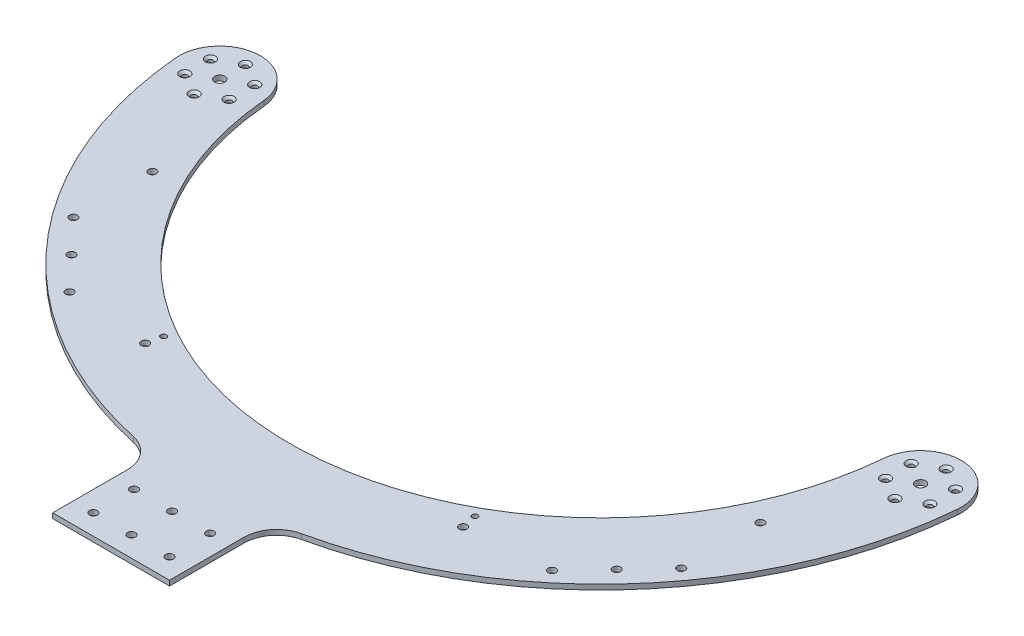
SolidWorks part; units mm, degrees
material "6061-T6 (SS)"
ref_plane "Front" through (0, 0, 0) normal (0, 0, 1) x (1, 0, 0)
ref_plane "Top" through (0, 0, 0) normal (0, 1, 0) x (1, 0, 0)
ref_plane "Right" through (0, 0, 0) normal (1, 0, 0) x (0, 0, -1)
sketch "Sketch1" plane through (0, 0, 0) normal (0, 1, 0) x (1, 0, 0)
  line L0 (36.5125, 0) -> (-36.5125, 0)
  line L1 (-36.5125, 0) -> (-36.5125, 63.5)
  line L2 (36.5125, 0) -> (36.5125, 63.5)
  circle A0 centre (0, 306.0691) radius 206.375 construction
  circle A1 centre (-219.075, 287.0191) radius 50.8 construction
  circle A2 centre (219.075, 287.0191) radius 50.8 construction
  arc A3 (-193.7705, 289.2195) -> (-244.3795, 284.8187) centre (-219.075, 287.0191) ccw
  arc A4 (-193.7705, 289.2195) -> (193.7705, 289.2195) centre (0, 306.0691) ccw
  arc A5 (-244.3795, 284.8187) -> (-36.5125, 63.5) centre (0, 306.0691) ccw
  arc A6 (244.3795, 284.8187) -> (193.7705, 289.2195) centre (219.075, 287.0191) ccw
  arc A7 (36.5125, 63.5) -> (244.3795, 284.8187) centre (0, 306.0691) ccw
  point P4 (0, 0)
  dimension "D1" = 412.75
  dimension "D2" = 101.6
  dimension "D3" = 19.05
  dimension "D4" = 25.4
  dimension "D5" = 38.1
  dimension "D6" = 0
  dimension "D7" = 73.025
  dimension "D8" = 63.5
extrude "Boss-Extrude1" add sketch "Sketch1" along normal blind 3.175
sketch "Sketch2" plane through (0, 3.175, 0) normal (0, 1, 0) x (1, 0, 0)
  circle A0 centre (-219.075, 287.0191) radius 3.175
  circle A1 centre (219.075, 287.0191) radius 3.175
  arc A2 (-193.7705, 289.2195) -> (-244.3795, 284.8187) centre (-219.075, 287.0191) ccw construction
  arc A4 (244.3795, 284.8187) -> (193.7705, 289.2195) centre (219.075, 287.0191) ccw construction
  dimension "D1" = 6.35
extrude "Cut-Extrude1" cut sketch "Sketch2" against normal through all
fillet "Fillet1" radius 20.32 2 edges at (36.5125, 1.5875, -63.5) (-36.5125, 1.5875, -63.5)
sketch "Sketch6" plane through (0, 3.175, 0) normal (0, 1, 0) x (1, 0, 0)
  line L1 (0, 306.0691) -> (0, 111.5674) construction
  circle A0 centre (219.075, 287.0191) radius 16 construction
  arc A2 (-193.7705, 289.2195) -> (193.7705, 289.2195) centre (0, 306.0691) ccw construction
  circle A3 centre (-219.075, 287.0191) radius 16 construction
  point P5 (219.075, 303.0191)
  point P13 (232.9314, 295.0191)
  point P14 (232.9314, 279.0191)
  point P15 (219.075, 271.0191)
  point P16 (205.2186, 279.0191)
  point P17 (205.2186, 295.0191)
  point P38 (-205.2186, 295.0191)
  point P39 (-205.2186, 279.0191)
  point P40 (-219.075, 271.0191)
  point P41 (-232.9314, 279.0191)
  point P42 (-232.9314, 295.0191)
  point P43 (-219.075, 303.0191)
  dimension "D2" = 32
  dimension "D1" = 6
hole_wizard "CSK for M3 Flat Head Machine Screw1" positions "Sketch6" profile "Sketch7" countersink size "M3" standard "ANSI Metric" end condition up to next
sketch "Sketch7" plane through (-219.075, 3.175, -303.0191) normal (1, 0, 0) x (0, 0, 1)
  line L0 (0, 0) -> (0, 3.175)
  line L1 (0, 3.175) -> (1.7, 3.175)
  line L2 (1.7, 3.175) -> (1.7, 1.45)
  line L3 (1.7, 1.45) -> (3.15, 0)
  line L5 (3.15, 0) -> (0, 0)
  line L6 (-1.7, 1.45) -> (-3.15, 0) construction
  line L11 (0, -6.35) -> (0, 107.95) construction
  dimension "Thru Hole Dia." = 3.4
  dimension "Thru Hole Depth" = 3.175
  dimension "Near C'Sink Dia." = 6.3
  dimension "Near C'Sink Angle" = 90
sketch "Sketch10" plane through (0, 3.175, 0) normal (0, 1, 0) x (1, 0, 0)
  line L1 (-36.5125, 0) -> (36.5125, 0) construction
  line L2 (-36.5125, 46.5986) -> (-36.5125, 0) construction
  line L3 (36.5125, 0) -> (36.5125, 46.5986) construction
  line L4 (-23.8125, 12.7) -> (0, 12.7) construction
  line L5 (0, 12.7) -> (23.8125, 12.7) construction
  point P0 (-23.8125, 12.7)
  point P2 (-23.8125, 38.1)
  point P4 (0, 38.1)
  point P6 (0, 12.7)
  point P8 (23.8125, 12.7)
  point P10 (23.8125, 38.1)
  dimension "D1" = 25.4
  dimension "D2" = 12.7
  dimension "D3" = 12.7
  dimension "D4" = 12.7
hole_wizard "#10 (0.1935) Diameter Hole1" positions "Sketch10" profile "Sketch9" hole size "#10" standard "ANSI Inch" end condition up to next
sketch "Sketch9" plane through (-23.8125, 3.175, -12.7) normal (1, 0, 0) x (0, 0, 1)
  line L0 (0, 0) -> (0, 3.175)
  line L1 (0, 3.175) -> (2.4574, 3.175)
  line L2 (2.4574, 3.175) -> (2.4574, 0)
  line L5 (2.4574, 0) -> (0, 0)
  line L11 (0, -6.35) -> (0, 107.95) construction
  dimension "Thru Hole Dia." = 4.9149
  dimension "Thru Hole Depth" = 3.175
sketch "Sketch13" plane through (0, 3.175, 0) normal (0, 1, 0) x (1, 0, 0)
  line L2 (189.988, 166.4439) -> (150.8125, 124.8338) construction
  line L4 (36.5125, 0) -> (36.5125, 46.5986) construction
  line L7 (0, 306.0691) -> (0, 111.5674) construction
  arc A0 (52.4848, 66.448) -> (244.3795, 284.8187) centre (0, 306.0691) ccw construction
  arc A1 (-193.7705, 289.2195) -> (193.7705, 289.2195) centre (0, 306.0691) ccw construction
  point P53 (150.8125, 124.8338)
  point P55 (170.4003, 145.6388)
  point P57 (189.988, 166.4439)
  point P71 (170.4003, 145.6388)
  point P97 (-150.8125, 124.8338)
  point P98 (-170.4003, 145.6388)
  point P99 (-189.988, 166.4439)
  dimension "D2" = 28.575
  dimension "D3" = 9.525
  dimension "D4" = 9.525
  dimension "D5" = 114.3
hole_wizard "#10 (0.1935) Diameter Hole2" positions "Sketch13" profile "Sketch12" hole size "#10" standard "ANSI Inch" end condition up to next
sketch "Sketch12" plane through (150.8125, 3.175, -124.8338) normal (1, 0, 0) x (0, 0, 1)
  line L0 (0, 0) -> (0, 3.175)
  line L1 (0, 3.175) -> (2.4574, 3.175)
  line L2 (2.4574, 3.175) -> (2.4574, 0)
  line L5 (2.4574, 0) -> (0, 0)
  line L11 (0, -6.35) -> (0, 107.95) construction
  dimension "Thru Hole Dia." = 4.9149
  dimension "Thru Hole Depth" = 3.175
sketch "Sketch16" plane through (0, 3.175, 0) normal (0, 1, 0) x (1, 0, 0)
  line L1 (0, 306.0691) -> (0, 111.5674) construction
  line L2 (-36.5125, 0) -> (36.5125, 0) construction
  line L3 (-99.3887, 120.65) -> (99.3887, 120.65) construction
  circle A0 centre (0, 306.0691) radius 210.3767 construction
  arc A1 (-193.7705, 289.2195) -> (193.7705, 289.2195) centre (0, 306.0691) ccw construction
  point P29 (99.3887, 120.65)
  point P31 (190.0734, 215.9)
  point P35 (-190.0734, 215.9)
  point P36 (-99.3887, 120.65)
  dimension "D1" = 15.875
  dimension "D3" = 120.65
  dimension "D4" = 215.9
other "AlignGroup1"
other "AlignGroup2"
hole_wizard "#10 (0.1935) Diameter Hole3" positions "Sketch16" profile "Sketch15" hole size "#10" standard "ANSI Inch" end condition up to next
sketch "Sketch15" plane through (-99.3887, 3.175, -120.65) normal (1, 0, 0) x (0, 0, 1)
  line L0 (0, 0) -> (0, 3.175)
  line L1 (0, 3.175) -> (2.4574, 3.175)
  line L2 (2.4574, 3.175) -> (2.4574, 0)
  line L5 (2.4574, 0) -> (0, 0)
  line L11 (0, -6.35) -> (0, 107.95) construction
  dimension "Thru Hole Dia." = 4.9149
  dimension "Thru Hole Depth" = 3.175
mirror "Mirror1" [suppressed] of bodies 114
delete or keep bodies "Body-Delete/Keep 1" [suppressed] type delete bodies bodies 114
ref_plane "Plane1" through (-50.8, 0, 0) normal (1, 0, 0) x (0, 0, -1)
sketch "Sketch20" plane through (0, 3.175, 0) normal (0, 1, 0) x (1, 0, 0)
  line L0 (0, -34.1305) -> (0, -156.3695) construction
  circle A2 centre (99.3887, 120.65) radius 2.4574 construction
  point P0 (97.3567, 130.175)
  point P15 (-97.3567, 130.175)
  dimension "D1" = 9.525
  dimension "D2" = 2.032
hole_wizard "#8 (0.199) Diameter Hole1" positions "Sketch20" profile "Sketch19" hole size "9/64" standard "ANSI Inch" end condition up to next
sketch "Sketch19" plane through (97.3567, 3.175, -130.175) normal (1, 0, 0) x (0, 0, 1)
  line L0 (0, 0) -> (0, 3.175)
  line L1 (0, 3.175) -> (1.786, 3.175)
  line L2 (1.786, 3.175) -> (1.786, 0)
  line L5 (1.786, 0) -> (0, 0)
  line L11 (0, -6.35) -> (0, 107.95) construction
  dimension "Thru Hole Dia." = 3.572
  dimension "Thru Hole Depth" = 3.175
